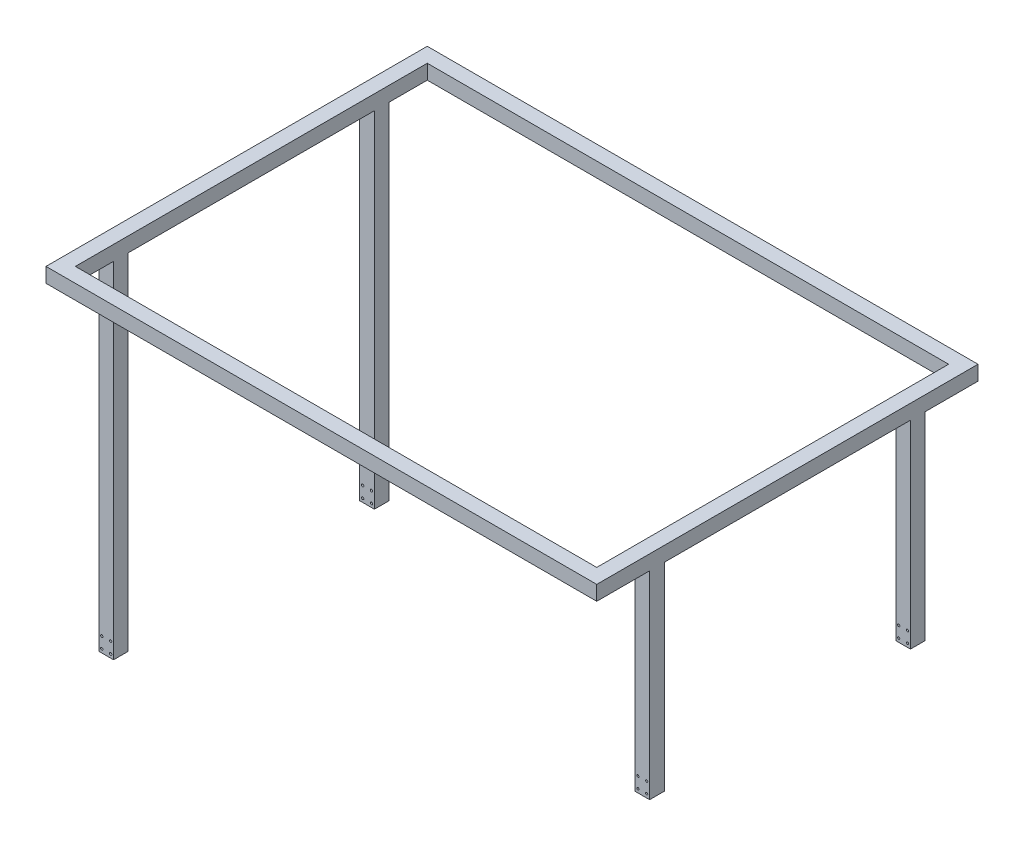
SolidWorks part; units mm, degrees
material "6061 合金"
ref_plane "前视基准面" through (0, 0, 0) normal (0, 0, 1) x (1, 0, 0)
ref_plane "上视基准面" through (0, 0, 0) normal (0, 1, 0) x (1, 0, 0)
ref_plane "右视基准面" through (0, 0, 0) normal (1, 0, 0) x (0, 0, -1)
sketch "草图1" plane through (0, 0, 0) normal (0, 1, 0) x (1, 0, 0)
  line L1 (-400.3658, 234.4582) -> (349.6342, 234.4582)
  line L2 (-400.3658, 234.4582) -> (-400.3658, -284.7418)
  line L3 (-400.3658, -284.7418) -> (349.6342, -284.7418)
  line L4 (349.6342, 234.4582) -> (349.6342, -284.7418)
  line L5 (329.6342, 214.4582) -> (-380.3658, 214.4582)
  line L6 (329.6342, 214.4582) -> (329.6342, -264.7418)
  line L7 (329.6342, -264.7418) -> (-380.3658, -264.7418)
  line L8 (-380.3658, 214.4582) -> (-380.3658, -264.7418)
  dimension "D1" = 750
  dimension "D2" = 519.2
  dimension "D3" = 20
  dimension "D4" = 20
  dimension "D5" = 20
  dimension "D6" = 20
extrude "凸台-拉伸1" add sketch "草图1" along normal blind 20
sketch "草图2" plane through (0, 0, 0) normal (0, -1, 0) x (1, 0, 0)
  line L0 (-400.3658, -234.4582) -> (-400.3658, 284.7418) construction
  line L5 (-380.3658, -214.4582) -> (-380.3658, 264.7418) construction
  line L6 (-400.3658, 284.7418) -> (349.6342, 284.7418) construction
  line L12 (-400.3658, 212.7418) -> (-380.3658, 212.7418)
  line L13 (-400.3658, 212.7418) -> (-400.3658, 192.7418)
  line L14 (-400.3658, 192.7418) -> (-380.3658, 192.7418)
  line L15 (-380.3658, 212.7418) -> (-380.3658, 192.7418)
  dimension "D6" = 20
  dimension "D7" = 72
extrude "凸台-拉伸2" add sketch "草图2" along normal blind 470
sketch "草图4" plane through (0, 0, 212.7418) normal (0, 0, 1) x (1, 0, 0)
  line L1 (-400.3658, -470) -> (-400.3658, 0) construction
  line L3 (-380.3658, -470) -> (-400.3658, -470) construction
  line L4 (-380.3658, -470) -> (-380.3658, 0) construction
  circle A0 centre (-396.3658, -465) radius 1.6
  circle A1 centre (-384.3658, -465) radius 1.6
  circle A2 centre (-396.3658, -450) radius 1.6
  circle A3 centre (-384.3658, -450) radius 1.6
  point P12 (-408.7628, -466.3592)
  point P13 (-395.8991, -460.0073)
  dimension "D1" = 4
  dimension "D3" = 12
  dimension "D5" = 15
  dimension "D6" = 12
  dimension "D2" = 5
  dimension "D7" = 3.2
  dimension "D8" = 4
  dimension "D9" = 5
  dimension "D4" = 15
ref_plane "基准面1" through (0, 0, 25.1418) normal (0, 0, 1) x (1, 0, 0)
sketch "草图6" plane through (0, 0, 0) normal (0, -1, 0) x (1, 0, 0)
  line L0 (349.6342, 284.7418) -> (349.6342, -234.4582) construction
  line L5 (329.6342, 264.7418) -> (329.6342, -214.4582) construction
  line L6 (349.6342, -234.4582) -> (-400.3658, -234.4582) construction
  line L12 (329.6342, -142.4582) -> (349.6342, -142.4582)
  line L13 (329.6342, -142.4582) -> (329.6342, -162.4582)
  line L14 (329.6342, -162.4582) -> (349.6342, -162.4582)
  line L15 (349.6342, -142.4582) -> (349.6342, -162.4582)
  dimension "D5" = 20
  dimension "D7" = 72
extrude "凸台-拉伸4" add sketch "草图6" along normal blind 270
sketch "草图7" plane through (0, 0, -162.4582) normal (0, 0, -1) x (-1, 0, 0)
  line L2 (-329.6342, -270) -> (-349.6342, -270) construction
  line L3 (-349.6342, -270) -> (-349.6342, 0) construction
  circle A0 centre (-345.6342, -265) radius 1.5
  circle A1 centre (-333.6342, -265) radius 1.5
  circle A2 centre (-345.6342, -250) radius 1.5
  circle A3 centre (-333.6342, -250) radius 1.5
  dimension "D1" = 5
  dimension "D2" = 4
  dimension "D4" = 15
  dimension "D5" = 4
  dimension "D6" = 12
  dimension "D7" = 15
  dimension "D8" = 5
  dimension "D3" = 12
extrude "Extrude1" cut sketch "草图4" against normal blind 30
extrude "Extrude2" cut sketch "草图7" against normal blind 30
mirror "Mirror1" about plane through (0, 0, 25.1418) normal (0, 0, 1) of "Extrude2", "Extrude1", "凸台-拉伸4", "凸台-拉伸2"
